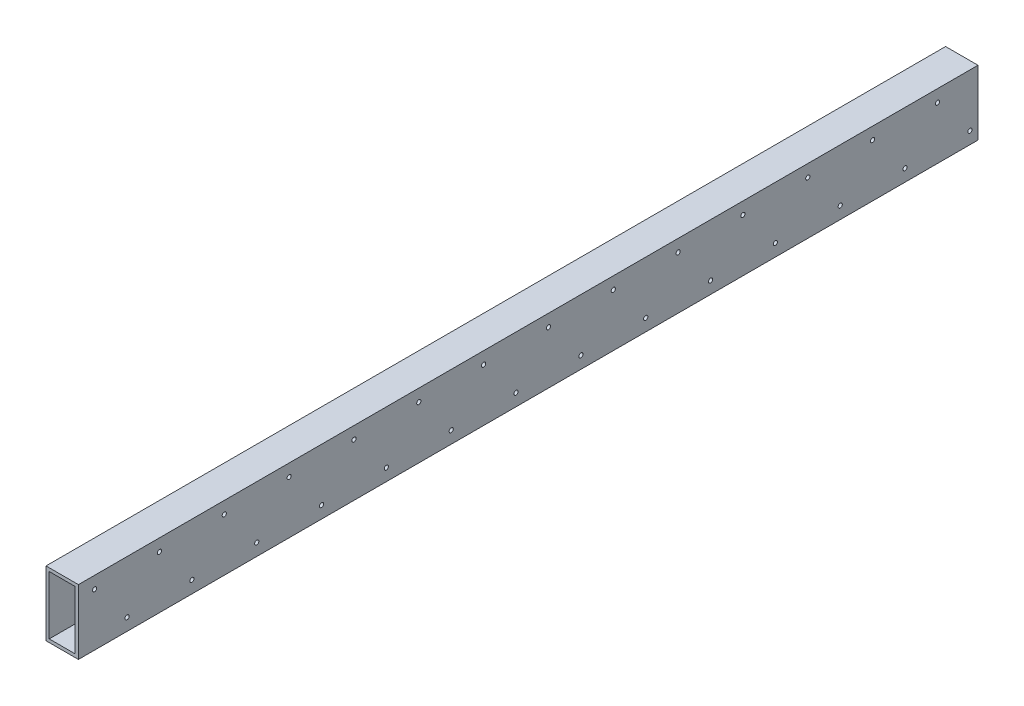
SolidWorks part; units mm, degrees
material "6061-T6 (SS)"
ref_plane "Front" through (0, 0, 0) normal (0, 0, 1) x (1, 0, 0)
ref_plane "Top" through (0, 0, 0) normal (0, 1, 0) x (1, 0, 0)
ref_plane "Right" through (0, 0, 0) normal (1, 0, 0) x (0, 0, -1)
sketch "Sketch1" plane through (0, 0, 0) normal (0, 0, 1) x (1, 0, 0)
  line L1 (-12.7, -25.4) -> (12.7, -25.4)
  line L2 (-12.7, -25.4) -> (-12.7, 25.4)
  line L3 (-12.7, 25.4) -> (12.7, 25.4)
  line L4 (12.7, -25.4) -> (12.7, 25.4)
  line L5 (-12.7, -25.4) -> (12.7, 25.4) construction
  line L6 (-12.7, 25.4) -> (12.7, -25.4) construction
  point P0 (0, 0)
  dimension "D1" = 50.8
  dimension "D2" = 25.4
extrude "Extrude-Thin1" add sketch "Sketch1" along normal blind 704.85 thin thin type one direction reverse wall 2.54
sketch "Sketch5" plane through (12.7, 0, 0) normal (1, 0, 0) x (0, 0, -1)
  line L0 (-704.85, -25.4) -> (0, -25.4) construction
  line L1 (0, -25.4) -> (0, 25.4) construction
  line L2 (-704.85, 25.4) -> (0, 25.4) construction
  point P98 (-6.35, -15.875)
  point P100 (-31.75, 15.875)
  point P112 (-57.15, -15.875)
  point P113 (-82.55, 15.875)
  point P114 (-107.95, -15.875)
  point P115 (-133.35, 15.875)
  point P116 (-158.75, -15.875)
  point P117 (-184.15, 15.875)
  point P118 (-209.55, -15.875)
  point P119 (-234.95, 15.875)
  point P120 (-260.35, -15.875)
  point P121 (-285.75, 15.875)
  point P122 (-311.15, -15.875)
  point P123 (-336.55, 15.875)
  point P124 (-361.95, -15.875)
  point P125 (-387.35, 15.875)
  point P126 (-412.75, -15.875)
  point P127 (-438.15, 15.875)
  point P128 (-463.55, -15.875)
  point P129 (-488.95, 15.875)
  point P130 (-514.35, -15.875)
  point P131 (-539.75, 15.875)
  point P132 (-565.15, -15.875)
  point P133 (-590.55, 15.875)
  point P134 (-615.95, -15.875)
  point P135 (-641.35, 15.875)
  point P136 (-666.75, -15.875)
  point P137 (-692.15, 15.875)
  dimension "D1" = 9.525
  dimension "D2" = 6.35
  dimension "D3" = 25.4
  dimension "D4" = 9.525
  dimension "D6" = 25.4
  dimension "D5" = 14
hole_wizard "1/8 (0.13) Diameter Hole1" positions "Sketch5" profile "Sketch4" hole size "1/8" standard "ANSI Inch" end condition up to next
sketch "Sketch4" plane through (12.7, -15.875, 6.35) normal (0, 1, 0) x (0, 0, -1)
  line L0 (0, 0) -> (0, 2.54)
  line L1 (0, 2.54) -> (1.651, 2.54)
  line L2 (1.651, 2.54) -> (1.651, 0)
  line L5 (1.651, 0) -> (0, 0)
  line L11 (0, -6.35) -> (0, 107.95) construction
  dimension "Thru Hole Dia." = 3.302
  dimension "Thru Hole Depth" = 2.54
